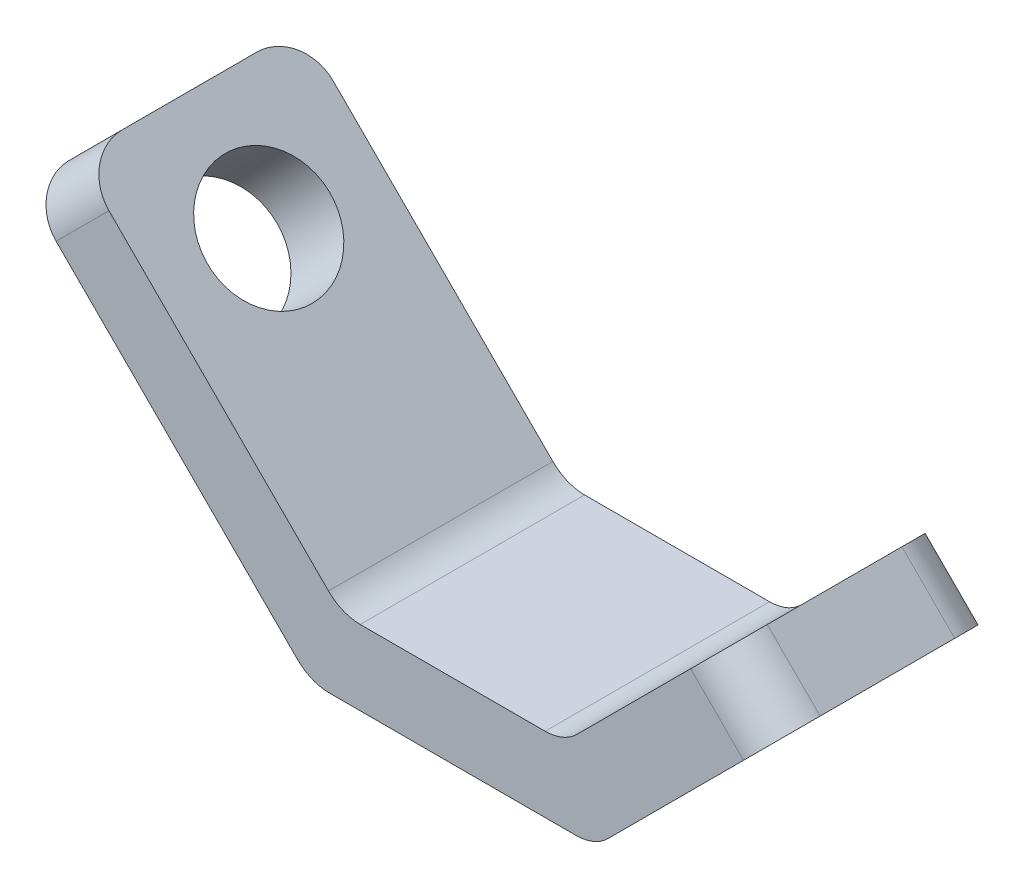
SolidWorks part; units mm, degrees
ref_plane "正面" through (0, 0, 0) normal (0, 0, 1) x (1, 0, 0)
ref_plane "平面" through (0, 0, 0) normal (0, 1, 0) x (1, 0, 0)
ref_plane "右側面" through (0, 0, 0) normal (1, 0, 0) x (0, 0, -1)
sketch "ｽｹｯﾁ1" plane through (0, 0, 0) normal (0, 0, 1) x (1, 0, 0)
  line L0 (0, 0) -> (-19.1421, 19.1421)
  line L1 (-19.1421, 19.1421) -> (-15.6066, 22.6777)
  line L2 (-15.6066, 22.6777) -> (2.0711, 5)
  line L3 (2.0711, 5) -> (16.9203, 5)
  line L4 (16.9203, 5) -> (27.5269, 15.6066)
  line L5 (27.5269, 15.6066) -> (31.0624, 12.0711)
  line L6 (31.0624, 12.0711) -> (18.9914, 0)
  line L7 (18.9914, 0) -> (0, 0)
  point P6 (-10.3033, 17.3744)
  point P10 (22.2236, 10.3033)
  dimension "D1" = 135
  dimension "D2" = 135
  dimension "D3" = 5
  dimension "D4" = 5
  dimension "D5" = 5
  dimension "D6" = 25
  dimension "D7" = 15
  dimension "D8" = 7.5
  dimension "D9" = 7.5
  dimension "D10" = 18
extrude "ﾎﾞｽ - 押し出し1" add sketch "ｽｹｯﾁ1" along normal mid plane 15
sketch "ｽｹｯﾁ2" plane through (0, 0, 0) normal (-0.7071, -0.7071, 0) x (0, 0, 1)
  line L1 (7.5, 27.0711) -> (-7.5, 27.0711) construction
  circle A0 centre (0, 19.5711) radius 4.1
  dimension "D1" = 8.2
  dimension "D2" = 7.5
extrude "ｶｯﾄ - 押し出し1" cut sketch "ｽｹｯﾁ2" against normal through all both and the other way through all
sketch "ｽｹｯﾁ3" plane through (9.4957, -9.4957, 0) normal (0.7071, -0.7071, 0) x (0, 0, -1)
  line L1 (-7.5, 30.5) -> (7.5, 30.5) construction
  circle A0 centre (0, 23) radius 4.1
  point P7 (0, 30.5)
  dimension "D1" = 8.2
  dimension "D2" = 7.5
extrude "ｶｯﾄ - 押し出し2" cut sketch "ｽｹｯﾁ3" against normal through all both and the other way through all
fillet "ﾌｨﾚｯﾄ1" radius 3 8 edges at (29.2947, 13.8388, -7.5) (29.2947, 13.8388, 7.5) (-17.3744, 20.9099, -7.5) (-17.3744, 20.9099, 7.5) (18.9914, 0, 0) (0, 0, 0) (16.9203, 5, 0) (2.0711, 5, 0)
equation "\"D4@ｽｹｯﾁ1\"=\"D3@ｽｹｯﾁ1\""
equation "\"D5@ｽｹｯﾁ1\"=\"D3@ｽｹｯﾁ1\""
